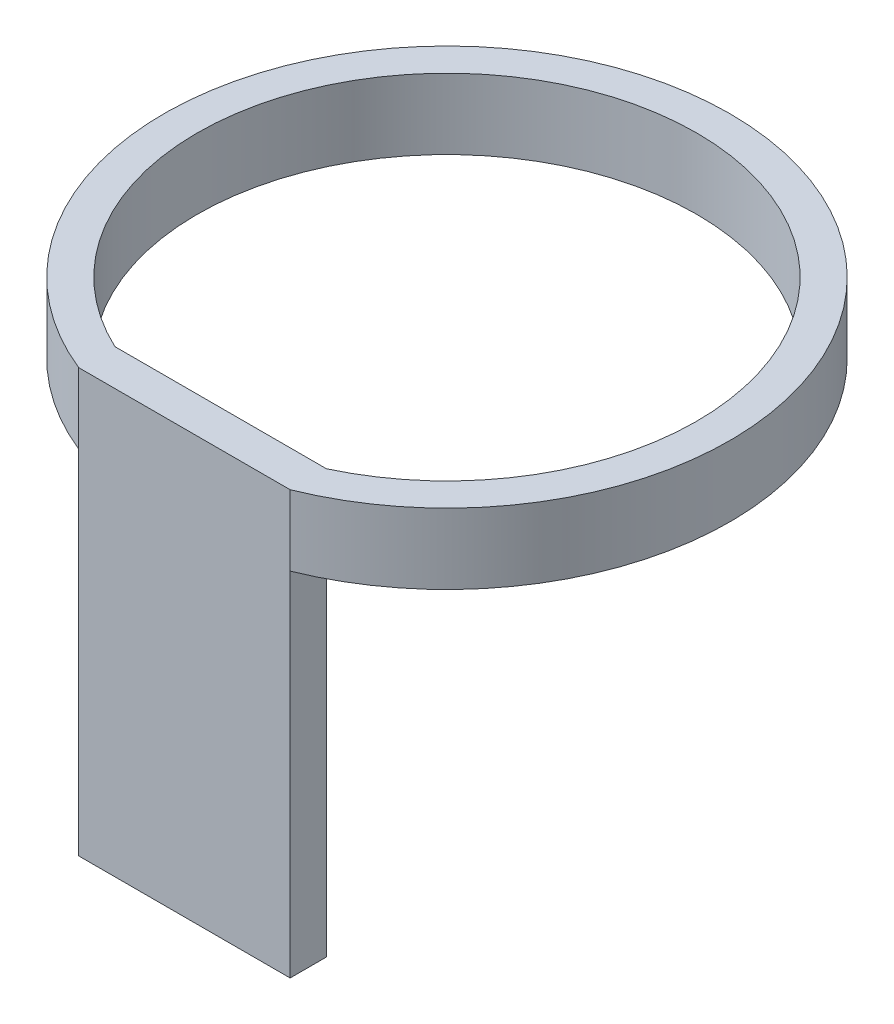
SolidWorks part; units mm, degrees
ref_plane "Front Plane" through (0, 0, 0) normal (0, 0, 1) x (1, 0, 0)
ref_plane "Top Plane" through (0, 0, 0) normal (0, 1, 0) x (1, 0, 0)
ref_plane "Right Plane" through (0, 0, 0) normal (1, 0, 0) x (0, 0, -1)
sketch "Sketch1" plane through (0, 0, 0) normal (0, 1, 0) x (1, 0, 0)
  circle A0 centre (0, 0) radius 102
  circle A1 centre (0, 0) radius 90
  dimension "D1" = 12
  dimension "D2" = 180
extrude "Boss-Extrude1" add sketch "Sketch1" against normal blind 25.4
sketch "Sketch2" plane through (0, -25.4, 0) normal (0, -1, 0) x (1, 0, 0)
  line L1 (0, 0) -> (0, 81.5377) construction
  line L3 (-38.1, 94.6171) -> (38.1, 94.6171)
  line L4 (-38.1, 81.5377) -> (38.1, 81.5377)
  line L5 (-38.1, 81.5377) -> (-38.1, 94.6171)
  line L6 (38.1, 81.5377) -> (38.1, 94.6171)
  circle A0 centre (0, 0) radius 90 construction
  circle A1 centre (0, 0) radius 102
  arc A2 (38.1, 94.6171) -> (-38.1, 94.6171) centre (0, 0) ccw construction
  arc A3 (38.1, 81.5377) -> (-38.1, 81.5377) centre (0, 0) ccw construction
  circle A4 centre (0, 0) radius 102 construction
  point P5 (38.1, 108.2379)
  point P12 (0, 81.5377)
  dimension "D2" = 76.2
  dimension "D1" = 0
extrude "Boss-Extrude2" add sketch "Sketch2" along normal blind 127
sketch "Sketch3" plane through (0, -25.4, 0) normal (0, -1, 0) x (1, 0, 0)
  line L1 (-38.1, 94.6171) -> (38.1, 94.6171)
  line L2 (-38.1, 94.6171) -> (38.1, 94.6171)
  arc A1 (38.1, 94.6171) -> (-38.1, 94.6171) centre (0, 0) ccw
  arc A2 (38.1, 94.6171) -> (-38.1, 94.6171) centre (0, 0) ccw
  dimension "D1" = 0
extrude "Cut-Extrude1" cut sketch "Sketch3" against normal through all
sketch "Sketch4" plane through (0, -25.4, 0) normal (0, 1, 0) x (1, 0, 0)
  line L3 (38.1, -81.5377) -> (-38.1, -81.5377)
  line L4 (38.1, -81.5377) -> (-38.1, -81.5377)
  arc A3 (-38.1, -81.5377) -> (38.1, -81.5377) centre (0, 0) ccw
  arc A5 (-38.1, -81.5377) -> (38.1, -81.5377) centre (0, 0) ccw
  dimension "D1" = 0
extrude "Boss-Extrude3" add sketch "Sketch4" along normal up to surface (25.4 mm away) contours L4 A5 region at (0, -25.4, 84.9366) up to face at (0, 0, -3.6915)
sketch "Sketch5" plane through (0, 0, 81.5377) normal (0, 0, -1) x (-1, 0, 0)
  line L0 (0, 0) -> (0, -117.6843)
  line L1 (-38.1, 0) -> (38.1, 0) construction
ref_axis "Axis1" through (0, -117.6843, 129.947) along (0, 0, -1)
